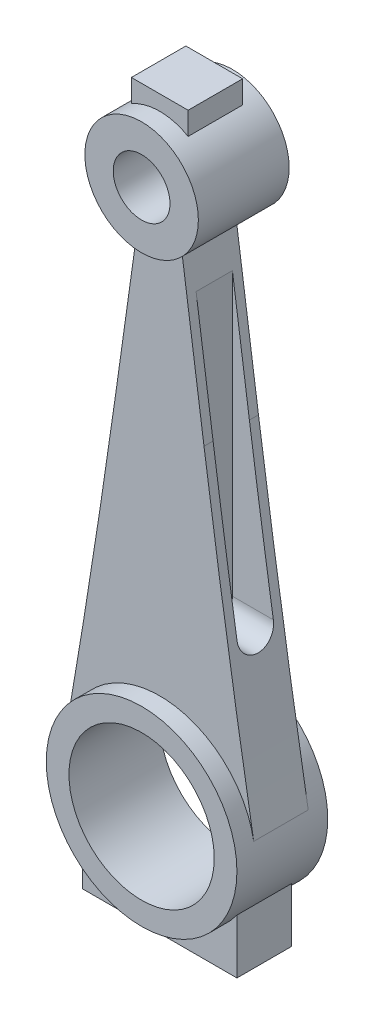
SolidWorks part; units mm, degrees
ref_plane "Front Plane" through (0, 0, 0) normal (0, 0, 1) x (1, 0, 0)
ref_plane "Top Plane" through (0, 0, 0) normal (0, 1, 0) x (1, 0, 0)
ref_plane "Right Plane" through (0, 0, 0) normal (1, 0, 0) x (0, 0, -1)
sketch "Sketch2" plane through (0, 0, 0) normal (0, 0, 1) x (1, 0, 0)
  line L0 (0, 150.0386) -> (0, -45.2121) construction
  line L1 (-9.7436, 73.4686) -> (-4.8247, 108.4686)
  line L2 (9.7436, 73.4686) -> (4.8247, 108.4686)
  line L3 (-6.25, 130.8253) -> (-6.25, 135.8253)
  line L4 (-6.25, 135.8253) -> (6.25, 135.8253)
  line L5 (6.25, 135.8253) -> (6.25, 130.8253)
  line L6 (-17, -12.3288) -> (-17, -24.3288)
  line L7 (-17, -24.3288) -> (17, -24.3288)
  line L8 (17, -24.3288) -> (17, -12.3288)
  circle A0 centre (0, 0) radius 16
  circle A1 centre (0, 0) radius 21
  circle A2 centre (0, 120) radius 6.25
  circle A3 centre (0, 120) radius 12.5
  arc A4 (-9.7436, 73.4686) -> (-20.6931, 3.5772) centre (-2230.3712, 385.5575) cw
  arc A5 (9.7436, 73.4686) -> (20.6931, 3.5772) centre (2230.3712, 385.5575) ccw
  dimension "D2" = 12.5
  dimension "D3" = 25
  dimension "D4" = 32
  dimension "D5" = 42
  dimension "D8" = 5
  dimension "D1" = 120
  dimension "D6" = 8
  dimension "D7" = 35
  dimension "D9" = 12.5
  dimension "D10" = 34
  dimension "D11" = 12
extrude "Boss-Extrude3" add sketch "Sketch2" along normal mid plane 20 contours L0 A3 A2 | A3 L0 A2 | L0 A1 A0 | A1 L0 A0 A3 region at (3.1629, 131.8041, 0) region at (-0.2795, 129.375, 0) region at (13.2231, 15.705, 0) region at (-0.4696, 18.5, 0)
extrude "Boss-Extrude4" add sketch "Sketch2<6>" along normal mid plane 12 contours L0 A3 L1 A4 A1 | A3 L0 A1 A5 L2 | A1 L0 L7 L8 | L0 A1 L6 L7 | L4 L0 A3 L5 | L0 L4 L3 A3 region at (3.3472, 133.8599, 0) region at (-3.3472, 133.8599, 0) region at (-6.6907, 53.7582, 0) region at (6.6907, 53.7582, 0) region at (-10.4494, -20.8498, 0) region at (10.4494, -20.8498, 0)
sketch "Sketch2<6>" plane through (0, 0, 0) normal (0, 0, 1) x (1, 0, 0) same geometry as "Sketch2"
sketch "Sketch3" plane through (0, 0, 0) normal (1, 0, 0) x (0, 0, -1)
  line L0 (0, 100) -> (0, 38) construction
  line L1 (4, 100) -> (4, 38)
  line L2 (-4, 100) -> (-4, 38)
  line L3 (-10, 120) -> (10, 120) construction
  line L4 (-10, 132.5) -> (-10, 107.5) construction
  line L5 (10, 107.5) -> (10, 132.5) construction
  arc A0 (4, 100) -> (-4, 100) centre (0, 100) ccw
  arc A1 (-4, 38) -> (4, 38) centre (0, 38) ccw
  point P3 (0, 69)
  dimension "D2" = 4
  dimension "D1" = 62
  dimension "D3" = 20
extrude "Cut-Extrude2" cut sketch "Sketch3" against normal through all from offset 6 offset against normal yes
extrude "Cut-Extrude3" cut sketch "Sketch3<2>" along normal through all from offset 6
sketch "Sketch3<2>" plane through (0, 0, 0) normal (1, 0, 0) x (0, 0, -1) same geometry as "Sketch3"
